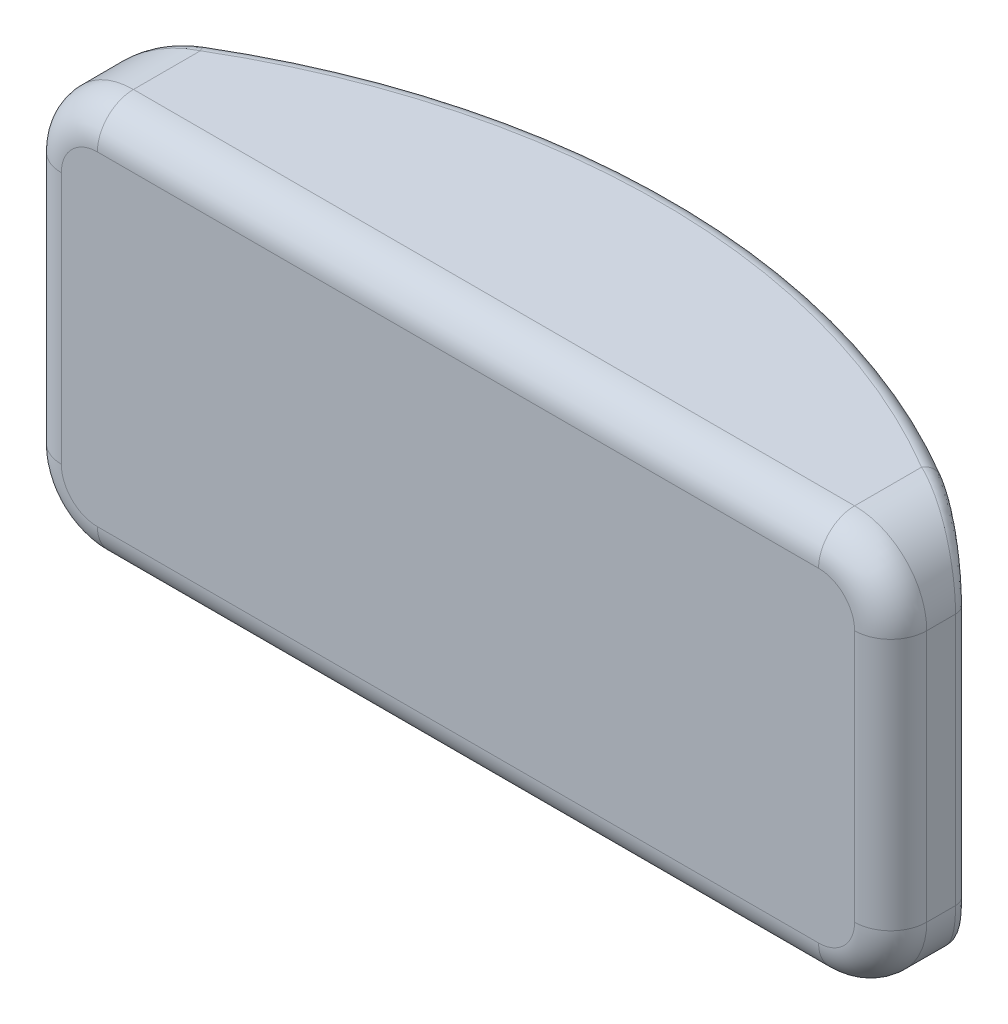
SolidWorks part; units mm, degrees
ref_plane "Front Plane" through (0, 0, 0) normal (0, 0, 1) x (1, 0, 0)
ref_plane "Top Plane" through (0, 0, 0) normal (0, 1, 0) x (1, 0, 0)
ref_plane "Right Plane" through (0, 0, 0) normal (1, 0, 0) x (0, 0, -1)
sketch "Sketch1" plane through (0, 0, 0) normal (0, 1, 0) x (1, 0, 0)
  line L1 (0, 0) -> (120, 0)
  line L2 (0, 0) -> (0, 30)
  line L3 (0, 30) -> (120, 30)
  line L4 (120, 0) -> (120, 30)
  arc A0 (0, 10) -> (120, 10) centre (60, -70) cw
  dimension "D1" = 120
  dimension "D2" = 30
  dimension "D3" = 10
  dimension "D4" = 10
extrude "Boss-Extrude1" add sketch "Sketch1" along normal blind 55 contours A0 L2 L1 L4 region at (60, 0, -12.5394)
fillet "Fillet1" radius 10 4 edges at (0, 0, -5) (0, 55, -5) (120, 55, -5) (120, 0, -5)
fillet "Fillet2" radius 5 8 edges at (2.9289, 52.0711, 0) (60, 55, 0) (117.0711, 52.0711, 0) (120, 27.5, 0) (117.0711, 2.9289, 0) (60, 0, 0) (2.9289, 2.9289, 0) (0, 27.5, 0)
fillet "Fillet3" radius 2 8 edges at (118.4387, 4.6345, -11.1475) (120, 27.5, -10) (117.46, 51.6595, -11.8435) (60, 55, -30) (1.5613, 50.3655, -11.1475) (0, 27.5, -10) (2.54, 3.3405, -11.8435) (60, 0, -30)
ref_plane "Plane1" through (0, 27.5, 0) normal (0, -1, 0) x (-1, 0, 0)
sketch "Sketch2" plane through (0, 27.5, 0) normal (0, -1, 0) x (-1, 0, 0)
  line L0 (-0.6, 9.2) -> (0, 8.75)
  line L1 (-60, 29) -> (-60, 30)
  line L4 (-120, 0) -> (0, 0)
  line L5 (-120, 30) -> (-120, 0)
  line L6 (0, 30) -> (-120, 30)
  line L7 (0, 0) -> (0, 30)
  line L8 (-120, 0) -> (0, 0)
  line L9 (-120, 30) -> (-120, 0)
  line L10 (0, 30) -> (-120, 30)
  line L11 (0, 0) -> (0, 30)
  arc A1 (0, 10) -> (-120, 10) centre (-60, -70) ccw construction
  arc A4 (0, 10) -> (-120, 10) centre (-60, -70) ccw
  arc A5 (-0.6, 9.2) -> (-119.4, 9.2) centre (-60, -70) ccw
  dimension "D1" = 0
  dimension "D2" = 1
extrude "Cut-Extrude1" cut sketch "Sketch2" against normal blind 0.5 and the other way blind 0.5 contours A5 L0 L11 A4 L1 region at (28.4922, 27.5, -24.5235)
sketch "Sketch3" plane through (0, 27.5, 0) normal (0, -1, 0) x (-1, 0, 0)
  line L0 (-0.6, 9.2) -> (0, 8.75) construction
  line L1 (-60, 29) -> (-60, 30) construction
  line L2 (-0.6, 9.2) -> (0, 8.75)
  line L3 (-60, 29) -> (-60, 30)
  line L4 (-120, 0) -> (0, 0)
  line L5 (0, 0) -> (0, 30)
  line L6 (0, 30) -> (-120, 30)
  line L7 (-120, 30) -> (-120, 0)
  line L8 (-120, 0) -> (0, 0)
  line L9 (0, 0) -> (0, 30)
  line L10 (0, 30) -> (-120, 30)
  line L11 (-120, 30) -> (-120, 0)
  arc A0 (-0.6, 9.2) -> (-119.4, 9.2) centre (-60, -70) ccw construction
  arc A1 (0, 10) -> (-120, 10) centre (-60, -70) ccw construction
  arc A2 (-0.6, 9.2) -> (-119.4, 9.2) centre (-60, -70) ccw
  arc A3 (0, 10) -> (-120, 10) centre (-60, -70) ccw
  circle A4 centre (-28.7595, 20) radius 9
  dimension "D2" = 18
  dimension "D3" = 10
  dimension "D1" = 0
extrude "Cut-Extrude2" cut sketch "Sketch3" against normal blind 3.5 and the other way blind 3.5 contours A2 A4 | A3 A4 | A3 A4 A2 region at (29.4016, 27.5, -18.1501) region at (27.4095, 27.5, -23.889) region at (26.6543, 27.5, -26.0648)
sketch "Sketch4" plane through (0, 27.5, 0) normal (0, -1, 0) x (-1, 0, 0)
  line L0 (-0.6, 9.2) -> (0, 8.75) construction
  line L1 (-60, 29) -> (-60, 30) construction
  line L2 (-0.6, 9.2) -> (0, 8.75)
  line L3 (-60, 29) -> (-60, 30)
  line L4 (-120, 0) -> (0, 0)
  line L5 (0, 0) -> (0, 30)
  line L6 (0, 30) -> (-120, 30)
  line L7 (-120, 30) -> (-120, 0)
  line L8 (-120, 0) -> (0, 0)
  line L9 (0, 0) -> (0, 30)
  line L10 (0, 30) -> (-120, 30)
  line L11 (-120, 30) -> (-120, 0)
  arc A0 (0, 10) -> (-120, 10) centre (-60, -70) ccw construction
  circle A1 centre (-28.7595, 20) radius 9
  circle A2 centre (-28.7595, 20) radius 9
  arc A3 (-0.6, 9.2) -> (-119.4, 9.2) centre (-60, -70) ccw construction
  arc A4 (0, 10) -> (-120, 10) centre (-60, -70) ccw
  arc A5 (-0.6, 9.2) -> (-119.4, 9.2) centre (-60, -70) ccw
  circle A6 centre (-28.7595, 20) radius 8
  dimension "D3" = 1
  dimension "D1" = 0
  dimension "D2" = 0
extrude "Boss-Extrude2" add sketch "Sketch4" along normal blind 2.5 and the other way blind 2.5 separate body contours A4 A6 A5 | A4 A6 | A5 A6 region at (29.2629, 27.5, -18.5496) region at (27.4005, 27.5, -23.9151) region at (26.7845, 27.5, -25.6896)
fillet "Fillet4" radius 2 2 edges at (28.7595, 25, -28) (28.7595, 30, -28)
